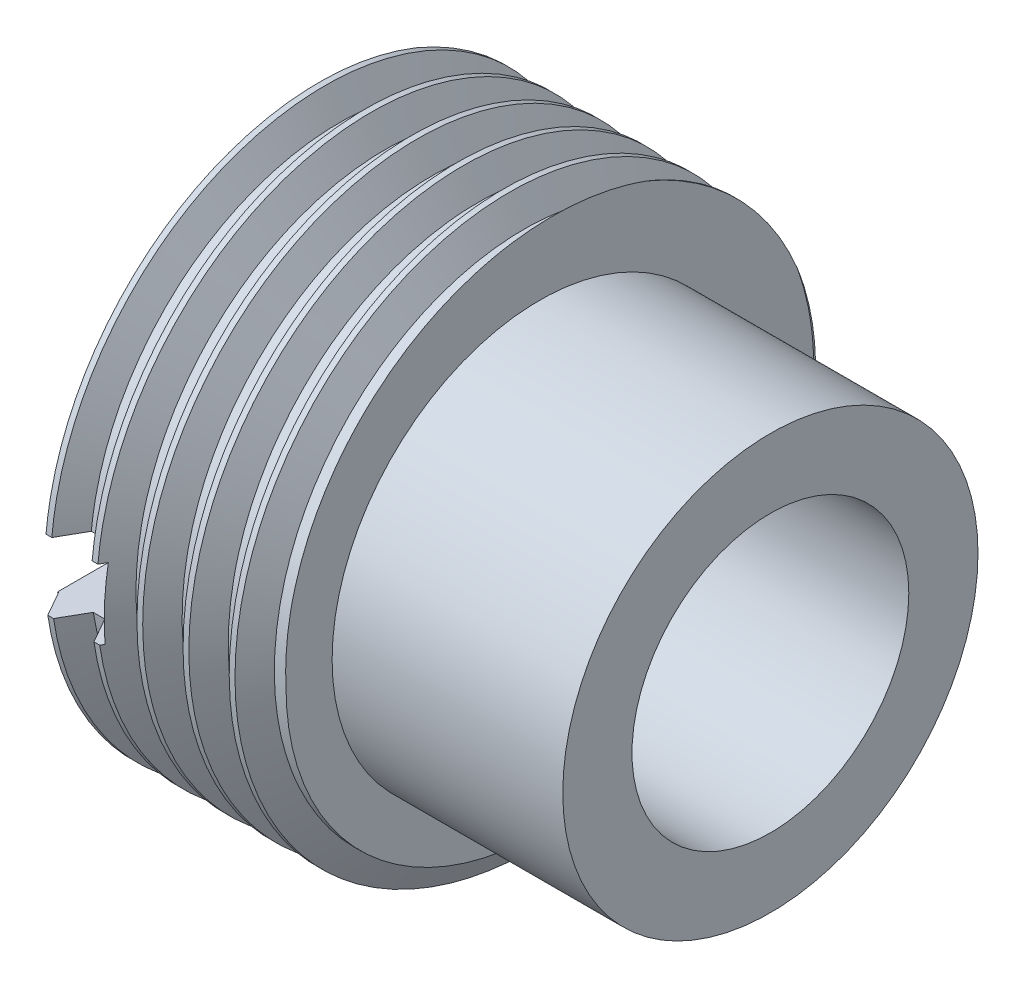
SolidWorks part; units mm, degrees
material "Cast Alloy Steel"
ref_plane "Front Plane" through (0, 0, 0) normal (0, 0, 1) x (1, 0, 0)
ref_plane "Top Plane" through (0, 0, 0) normal (0, 1, 0) x (1, 0, 0)
ref_plane "Right Plane" through (0, 0, 0) normal (1, 0, 0) x (0, 0, -1)
sketch "Sketch1" plane through (0, 0, 0) normal (0, 0, 1) x (1, 0, 0)
  line L0 (10, 6) -> (-10, 6)
  line L1 (-10, 6) -> (-10, 11)
  line L2 (-10, 11) -> (0, 11)
  line L3 (0, 11) -> (0, 9)
  line L4 (0, 9) -> (10, 9)
  line L5 (10, 9) -> (10, 6)
  line L6 (10, 0) -> (-10, 0) construction
  point P4 (0, 6)
  point P8 (-5, 11)
  point P11 (0, 0)
  dimension "D1" = 20
  dimension "D2" = 12
  dimension "D3" = 22
  dimension "D4" = 18
  dimension "D5" = 10
revolve "Revolve1" add sketch "Sketch1" angle 360 about L6
thread "Thread1" pitch 2 method extrude trim with start face yes trim with end face yes profile "Thread Profile1" start angle 0, offset 1, length 0, pitch 2, diameter 22
ref_plane "Plane1" through (-11, 0, -11) normal (0, -1, 0) x (0, 0, -1)
sketch "Thread Profile1" plane through (-11, 0, -11) normal (0, -1, 0) x (0, 0, -1)
  line L0 (0, 0) -> (0, 2) construction
  line L1 (0, 0) -> (1.0825, 0.625)
  line L2 (1.0825, 0.625) -> (1.0825, 0.875)
  line L3 (1.0825, 0.875) -> (0, 1.5)
  line L4 (1.0825, 0.75) -> (0, 0.75) construction
  line L11 (0, 0) -> (0, 1.5)
  point P2 (0, 0)
  dimension "Pitch" = 2
  dimension "Profile_Angle" = 60
  dimension "Profile_Land" = 0.25
  dimension "Profile_Height" = 1.0825
sketch "Sketch2" plane through (0, 0, 0) normal (0, 0, 1) x (1, 0, 0)
  line L0 (-10, 0) -> (-7, 0)
  line L2 (-10, 6) -> (-10, -6) construction
  dimension "D1" = 3
extrude "Cut-Extrude-Thin1" cut sketch "Sketch2" against normal through all both and the other way through all thin contours L0 thin type mid plane wall 3
